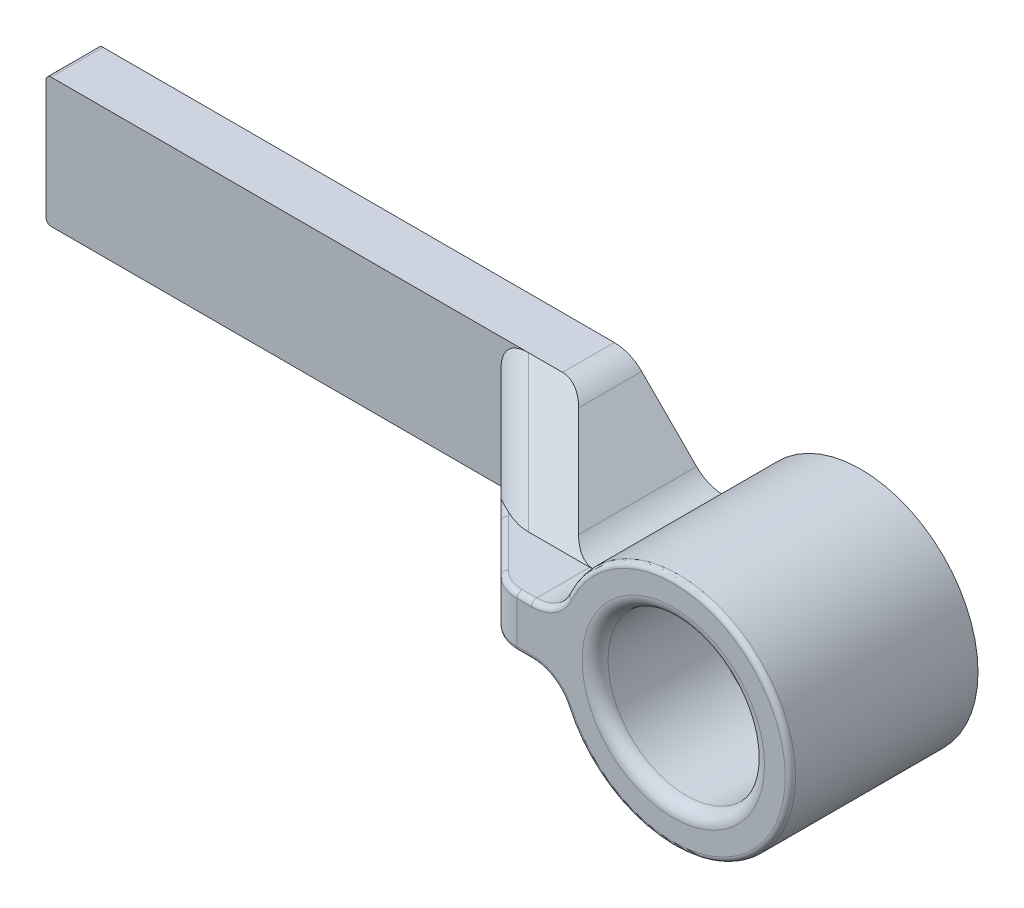
SolidWorks part; units mm, degrees
ref_plane "前视基准面" through (0, 0, 0) normal (0, 0, 1) x (1, 0, 0)
ref_plane "上视基准面" through (0, 0, 0) normal (0, 1, 0) x (1, 0, 0)
ref_plane "右视基准面" through (0, 0, 0) normal (1, 0, 0) x (0, 0, -1)
other "Configuration Table"
sketch "草图1" plane through (0, 0, 0) normal (0, 0, 1) x (1, 0, 0)
  circle A0 centre (0, 0) radius 6.05
  circle A1 centre (0, 0) radius 9.05
  dimension "D1" = 12.1
  dimension "D2" = 3
extrude "凸台-拉伸1" add sketch "草图1" along normal blind 13
sketch "草图2" plane through (0, 0, 0) normal (0, 0, -1) x (-1, 0, 0)
  circle A0 centre (0, 0) radius 6.05
  circle A1 centre (0, 0) radius 9.05
  dimension "D1" = 12.1
  dimension "D2" = 18.1
extrude "凸台-拉伸2" add sketch "草图2" along normal blind 1.5
sketch "草图3" plane through (0, 0, -1.5) normal (0, 0, -1) x (-1, 0, 0)
  line L1 (7, 2) -> (59, 2)
  line L2 (7, 2) -> (7, -2)
  line L3 (7, -2) -> (59, -2)
  line L4 (59, 2) -> (59, -2)
  circle A0 centre (0, 0) radius 6.05 construction
  dimension "D1" = 2
  dimension "D2" = 2
  dimension "D3" = 7
  dimension "D4" = 52
extrude "凸台-拉伸3" add sketch "草图3" against normal up to surface (14.5 mm away) up to face at (9.05, 0, 13)
sketch "草图4" plane through (0, 0, -1.5) normal (0, 0, -1) x (-1, 0, 0)
  line L0 (8.8262, -2) -> (59, -2) construction
  line L1 (17.8262, 8) -> (59, 8)
  line L2 (17.8262, 8) -> (17.8262, -2)
  line L3 (17.8262, -2) -> (59, -2)
  line L4 (59, 8) -> (59, -2)
  line L5 (59, 2) -> (8.8262, 2) construction
  line L6 (59, -2) -> (59, 2) construction
  dimension "D1" = 9
  dimension "D2" = 0
  dimension "D3" = 6
  dimension "D4" = 0
extrude "凸台-拉伸4" add sketch "草图4" against normal blind 4
sketch "草图5" plane through (0, 2, 0) normal (0, 1, 0) x (1, 0, 0)
  line L0 (-59, -13) -> (-8.8262, -13) construction
  line L1 (-59, -2.5) -> (-17.8262, -2.5)
  line L2 (-59, -2.5) -> (-59, -13)
  line L3 (-59, -13) -> (-17.8262, -13)
  line L4 (-17.8262, -2.5) -> (-17.8262, -13)
  line L5 (-17.8262, -2.5) -> (-17.8262, 1.5) construction
  dimension "D1" = 0
extrude "切除-拉伸1" cut sketch "草图5" against normal blind 4
chamfer "倒角1" distance 6 angle 45 1 edges at (-17.8262, 2, 0.5)
chamfer "倒角2" distance 6 angle 45 1 edges at (-17.8262, 0, 2.5)
chamfer "倒角3" distance 6 angle 45 1 edges at (-17.8262, 2, 2.5)
chamfer "倒角4" distance 4.5 angle 45 1 edges at (-17.8262, 0, 13)
fillet "圆角1" radius 3 6 edges at (-8.8262, 2, 5.75) (-8.8262, -2, 5.75) (-11.8262, 2, 3.5) (-20.8262, 5, 5.5) (-17.8262, 8, 0.5) (-13.3262, 0, 13)
ref_plane "基准面1" through (0, 0, 4) normal (0, 0, 1) x (1, 0, 0)
sketch "草图6" plane through (0, 0, 4) normal (0, 0, 1) x (1, 0, 0)
  circle A0 centre (0, 0) radius 6.05
  circle A1 centre (0, 0) radius 5.9
  dimension "D1" = 12.1
  dimension "D2" = 11.8
extrude "凸台-拉伸5" add sketch "草图6" against normal blind 2
fillet "圆角2" radius 1 2 edges at (5.9, 0, 4) (5.9, 0, 2)
fillet "圆角3" radius 1 1 edges at (6.05, 0, 13)
fillet "圆角4" radius 0.4 11 edges at (-20.8262, -2, 5.5) (-16.0156, -2, 10.3107) (-13.2316, -2, 12.7716) (-11.5236, -2, 13) (-9.3411, -2.4767, 13) (-18.8869, 2, 7.4393) (-16.0156, 2, 10.3107) (-13.2316, 2, 12.7716) (-11.5236, 2, 13) (-9.3411, 2.4767, 13) (9.05, 0, 13)
fillet "圆角5" radius 0.4 2 edges at (-59, 8, 0.5) (-59, -2, 0.5)
